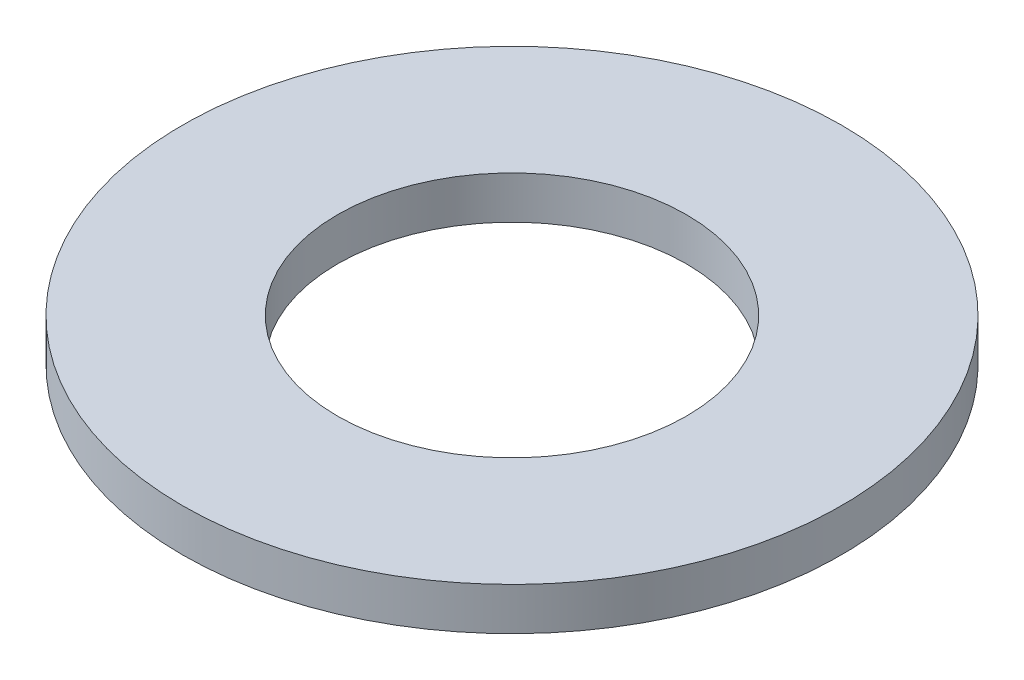
SolidWorks part; units mm, degrees
ref_plane "Front Plane" through (0, 0, 0) normal (0, 0, 1) x (1, 0, 0)
ref_plane "Top Plane" through (0, 0, 0) normal (0, 1, 0) x (1, 0, 0)
ref_plane "Right Plane" through (0, 0, 0) normal (1, 0, 0) x (0, 0, -1)
sketch "Sketch1" plane through (0, 0, 0) normal (0, 1, 0) x (1, 0, 0)
  circle A0 centre (0, 0) radius 85
  dimension "FLANGE_OD" = 170
extrude "Boss-Extrude1" add sketch "Sketch1" along normal blind 11
sketch "Sketch2" plane through (0, 0, 0) normal (0, 1, 0) x (1, 0, 0)
  circle A0 centre (0, 0) radius 45
  dimension "BORE_D" = 90
extrude "Cut-Extrude1" cut sketch "Sketch2" along normal through all
sketch "Sketch3" plane through (0, 11, 0) normal (0, 1, 0) x (1, 0, 0)
  circle A0 centre (0, 0) radius 37.2452 construction
  circle A1 centre (-37.2452, 0) radius 1.649
  dimension "BOLT_D" = 3.2979
  dimension "BOLT_PCD" = 74.4905
extrude "Cut-Extrude2" cut sketch "Sketch3" against normal blind 8.3305 rebuild error yes
pattern_circular "CirPattern1" count 8 over 360 rebuild error yes
